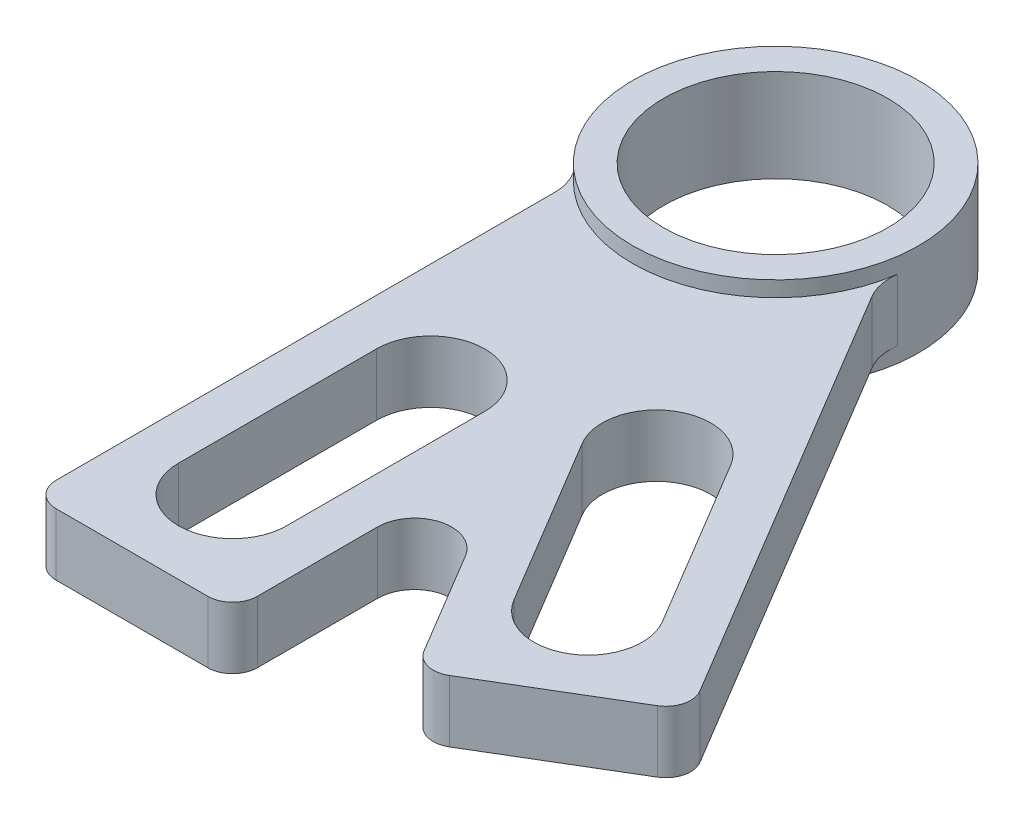
SolidWorks part; units mm, degrees
material "AISI 4130 Steel, normalized at 870C"
ref_plane "Front Plane" through (0, 0, 0) normal (0, 0, 1) x (1, 0, 0)
ref_plane "Top Plane" through (0, 0, 0) normal (0, 1, 0) x (1, 0, 0)
ref_plane "Right Plane" through (0, 0, 0) normal (1, 0, 0) x (0, 0, -1)
sketch "Sketch1" plane through (0, 0, 0) normal (0, 1, 0) x (1, 0, 0)
  line L0 (0, 0) -> (0, -66.04) construction
  line L1 (0, 0) -> (33.8811, -56.6864) construction
  line L2 (0, -55.7213) -> (0, -35.4013) construction
  line L3 (-5.5562, -55.7213) -> (-5.5562, -35.4013)
  line L4 (5.5563, -55.7213) -> (5.5563, -35.4013)
  line L5 (28.5872, -47.8292) -> (18.1622, -30.3872) construction
  line L6 (23.8179, -50.6798) -> (13.3929, -33.2378)
  line L7 (33.3565, -44.9786) -> (22.9315, -27.5366)
  line L8 (0, -66.04) -> (0, -61.2775) construction
  line L9 (33.8811, -56.6864) -> (31.4377, -52.5985) construction
  line L10 (-10.3187, -66.04) -> (10.3188, -66.04)
  line L11 (25.0238, -61.9804) -> (42.7384, -51.3925)
  line L12 (-10.3187, -66.04) -> (-10.3187, -10.4432)
  line L13 (10.3188, -66.04) -> (10.3188, -37.3773)
  line L14 (42.7384, -51.3925) -> (14.215, -3.6702)
  line L15 (25.0238, -61.9804) -> (10.3188, -37.3773)
  line L16 (185.4192, -310.2249) -> (17.7009, -29.6154) construction
  line L22 (0, 0) -> (10.3188, -37.3773) construction
  circle A0 centre (0, 0) radius 11.5062
  circle A1 centre (0, 0) radius 14.6812
  arc A2 (-5.5562, -55.7213) -> (5.5563, -55.7213) centre (0, -55.7213) ccw
  arc A3 (5.5563, -35.4013) -> (-5.5562, -35.4013) centre (0, -35.4013) ccw
  arc A4 (23.8179, -50.6798) -> (33.3565, -44.9786) centre (28.5872, -47.8292) ccw
  arc A5 (22.9315, -27.5366) -> (13.3929, -33.2378) centre (18.1622, -30.3872) ccw
  point P8 (0, -45.5613)
  point P13 (23.3747, -39.1082)
  point P25 (0, -66.04)
  point P27 (33.8811, -56.6864)
  dimension "D2" = 29.3624
  dimension "D3" = 4.7625
  dimension "D4" = 4.7625
  dimension "D5" = 20.32
  dimension "D6" = 66.04
  dimension "D7" = 20.6375
extrude "Bearing_Insert_Extrude" add sketch "Sketch1" along normal mid plane 9.525 contours A1 A0 region at (-5.4988, 0, -13.1636)
extrude "Apex_Slot_Insert_Extrude" add sketch "Sketch1<4>" along normal mid plane 6.35 contours A1 L12 L10 L13 L15 L11 L14 A5 L7 A4 L6 A3 L4 A2 L3 | L13 L15 region at (9.989, 0, 36.1828)
sketch "Sketch1<4>" plane through (0, 0, 0) normal (0, 1, 0) x (1, 0, 0) same geometry as "Sketch1"
fillet "Fillet1" radius 5.08 2 edges at (14.215, 0, 3.6702) (-10.3187, 0, 10.4432)
fillet "Fillet2" radius 2.54 4 edges at (42.7384, 0, 51.3925) (25.0238, 0, 61.9804) (10.3188, 0, 66.04) (-10.3187, 0, 66.04)
fillet "Fillet3" radius 3.81 1 edges at (10.3188, 0, 37.3773)
equation "\"Apex_thickness\"= .25"
equation "\"Bearing_diameter\"= 0.906in"
equation "\"A-arm_angle\"= 39.1893"
equation "\"D1@Sketch1\"=\"Bearing_diameter\""
equation "\"D1@Apex_Slot_Insert_Extrude\"=\"Apex_thickness\""
